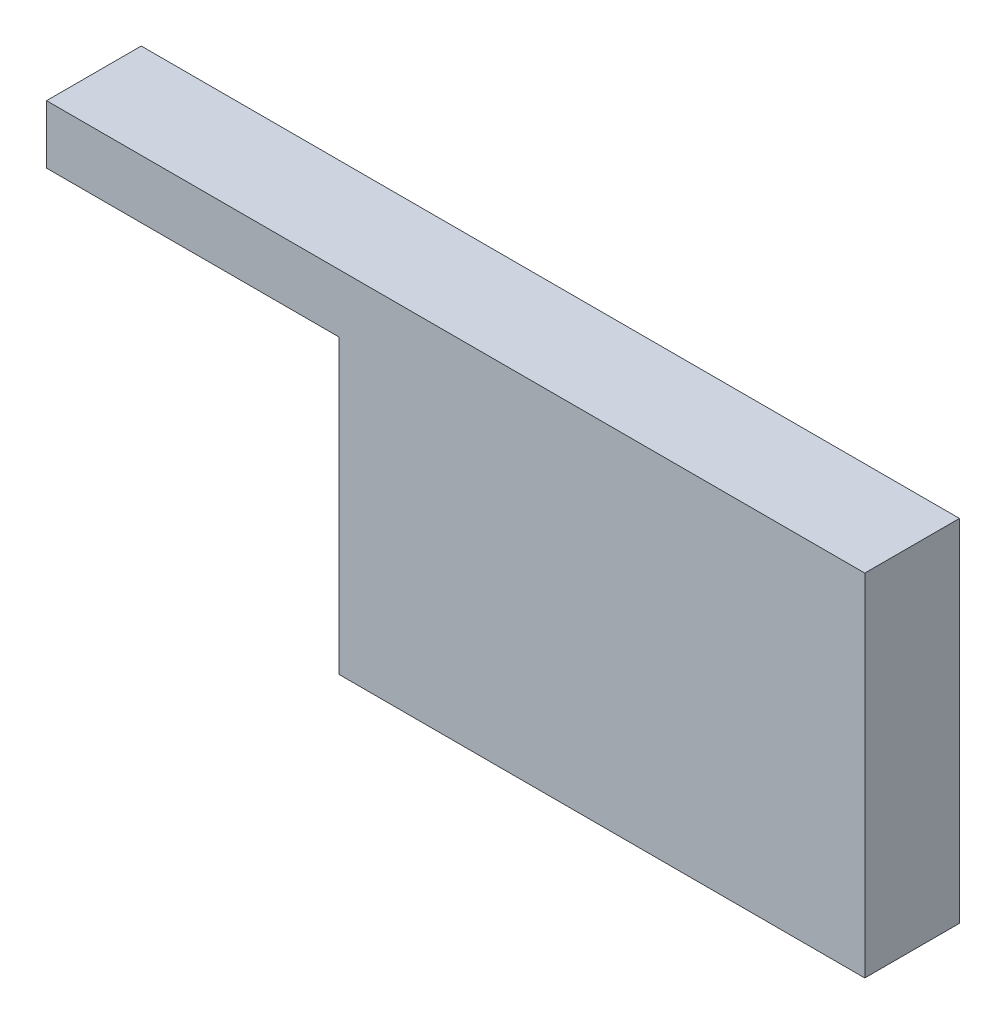
SolidWorks part; units mm, degrees
ref_plane "Plan de face" through (0, 0, 0) normal (0, 0, 1) x (1, 0, 0)
ref_plane "Plan de dessus" through (0, 0, 0) normal (0, 1, 0) x (1, 0, 0)
ref_plane "Plan de droite" through (0, 0, 0) normal (1, 0, 0) x (0, 0, -1)
sketch "Esquisse1" plane through (0, 0, 0) normal (0, 0, 1) x (1, 0, 0)
  line L1 (0, 0) -> (45, 0)
  line L2 (0, 0) -> (0, 30)
  line L3 (0, 30) -> (45, 30)
  line L4 (45, 0) -> (45, 30)
  dimension "D1" = 45
  dimension "D2" = 30
extrude "Boss.-Extru.1" add sketch "Esquisse1" along normal blind 8.1
sketch "Esquisse2" plane through (0, 0, 8.1) normal (0, 0, 1) x (1, 0, 0)
  line L1 (0, 30) -> (-25, 30)
  line L2 (0, 30) -> (0, 25)
  line L3 (0, 25) -> (-25, 25)
  line L4 (-25, 30) -> (-25, 25)
  dimension "D1" = 5
  dimension "D2" = 25
extrude "Boss.-Extru.2" add sketch "Esquisse2" against normal up to vertex (8.1 mm away) up to point (0, 30, 0)
sketch "Esquisse3" plane through (0, 0, 8.1) normal (0, 0, 1) x (1, 0, 0)
  line L0 (-22.5526, 28.1071) -> (-4.7113, 28.1071) construction
  circle A0 centre (-4.7113, 28.1071) radius 1.4085
  circle A1 centre (-22.5526, 28.1071) radius 1
  dimension "D1" = 2
